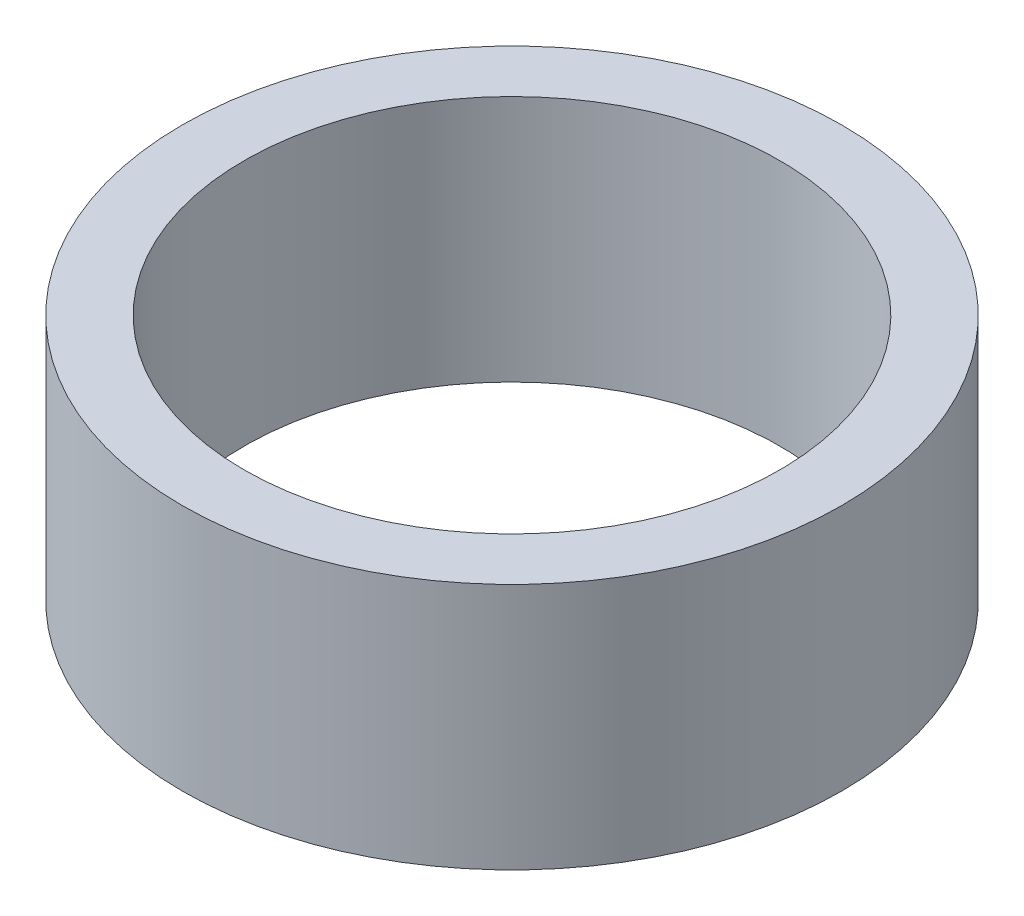
SolidWorks part; units mm, degrees
ref_plane "Front Plane" through (0, 0, 0) normal (0, 0, 1) x (1, 0, 0)
ref_plane "Top Plane" through (0, 0, 0) normal (0, 1, 0) x (1, 0, 0)
ref_plane "Right Plane" through (0, 0, 0) normal (1, 0, 0) x (0, 0, -1)
sketch "Sketch1" plane through (0, 0, 0) normal (0, 1, 0) x (1, 0, 0)
  circle A0 centre (0, 0) radius 40
  dimension "FLANGE_OD" = 80
extrude "Boss-Extrude1" add sketch "Sketch1" along normal blind 30
sketch "Sketch2" plane through (0, 0, 0) normal (0, 1, 0) x (1, 0, 0)
  circle A0 centre (0, 0) radius 32.5
  dimension "BORE_D" = 65
extrude "Cut-Extrude1" cut sketch "Sketch2" along normal through all
sketch "Sketch3" plane through (0, 30, 0) normal (0, 1, 0) x (1, 0, 0)
  circle A0 centre (0, 0) radius 18.1801 construction
  circle A1 centre (-18.1801, 0) radius 1.5
  dimension "BOLT_D" = 3
  dimension "BOLT_PCD" = 36.3602
extrude "Cut-Extrude2" cut sketch "Sketch3" against normal blind 28.1957 rebuild error yes
pattern_circular "CirPattern1" count 6 over 360 rebuild error yes
